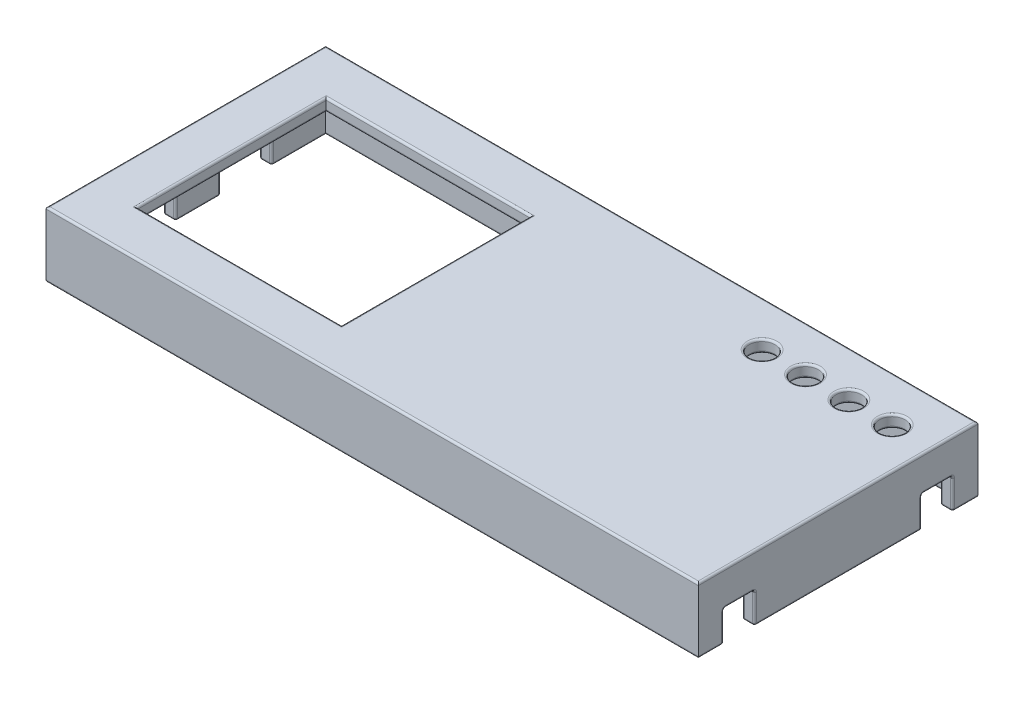
SolidWorks part; units mm, degrees
ref_plane "Front Plane" through (0, 0, 0) normal (0, 0, 1) x (1, 0, 0)
ref_plane "Top Plane" through (0, 0, 0) normal (0, 1, 0) x (1, 0, 0)
ref_plane "Right Plane" through (0, 0, 0) normal (1, 0, 0) x (0, 0, -1)
sketch "Sketch1" plane through (0, 0, 0) normal (0, 1, 0) x (1, 0, 0)
  line L0 (-2.4, 2.4) -> (-2.4, -52.4)
  line L1 (0, 0) -> (123, 0)
  line L2 (0, 0) -> (0, -50)
  line L3 (0, -50) -> (123, -50)
  line L4 (123, 0) -> (123, -50)
  line L5 (-2.4, -52.4) -> (125.4, -52.4)
  line L6 (125.4, 2.4) -> (125.4, -52.4)
  line L7 (-2.4, 2.4) -> (125.4, 2.4)
  dimension "D1" = 50
  dimension "D2" = 123
  dimension "D3" = 2.4
extrude "Boss-Extrude1" add sketch "Sketch1" along normal blind 10.4
sketch "Sketch2" plane through (0, 10.4, 0) normal (0, 1, 0) x (1, 0, 0)
  line L1 (-2.4, 2.4) -> (125.4, 2.4)
  line L2 (-2.4, 2.4) -> (-2.4, -52.4)
  line L3 (-2.4, -52.4) -> (125.4, -52.4)
  line L4 (125.4, 2.4) -> (125.4, -52.4)
extrude "Boss-Extrude2" add sketch "Sketch2" along normal blind 2.4
sketch "Sketch3" plane through (-2.4, 0, 0) normal (-1, 0, 0) x (0, 0, 1)
  line L0 (-2.4, 0) -> (52.4, 0) construction
  line L1 (10.6, 0) -> (20.6, 0)
  line L2 (10.6, 0) -> (10.6, 5)
  line L3 (10.6, 5) -> (20.6, 5)
  line L4 (20.6, 0) -> (20.6, 5)
  line L5 (-2.4, 12.8) -> (-2.4, 0) construction
  line L6 (29.4, 0) -> (39.4, 0)
  line L7 (29.4, 0) -> (29.4, 5)
  line L8 (29.4, 5) -> (39.4, 5)
  line L9 (39.4, 0) -> (39.4, 5)
  line L10 (52.4, 12.8) -> (52.4, 0) construction
  dimension "D1" = 10
  dimension "D2" = 10
  dimension "D3" = 5
  dimension "D4" = 5
  dimension "D5" = 13
  dimension "D6" = 13
extrude "Cut-Extrude1" cut sketch "Sketch3" against normal blind 10
sketch "Sketch4" plane through (0, 12.8, 0) normal (0, 1, 0) x (1, 0, 0)
  line L0 (-2.4, 2.4) -> (-2.4, -52.4) construction
  line L1 (6.6, -6.5) -> (46.6, -6.5)
  line L2 (6.6, -6.5) -> (6.6, -43.5)
  line L3 (6.6, -43.5) -> (46.6, -43.5)
  line L4 (46.6, -6.5) -> (46.6, -43.5)
  line L5 (125.4, 2.4) -> (-2.4, 2.4) construction
  dimension "D1" = 37
  dimension "D2" = 40
  dimension "D3" = 9
  dimension "D4" = 8.9
extrude "Cut-Extrude2" cut sketch "Sketch4" against normal blind 10
sketch "Sketch5" plane through (125.4, 0, 0) normal (1, 0, 0) x (0, 0, -1)
  line L0 (-52.4, 0) -> (2.4, 0) construction
  line L1 (-8.6, 0) -> (-2.6, 0)
  line L2 (-8.6, 0) -> (-8.6, 6)
  line L3 (-8.6, 6) -> (-2.6, 6)
  line L4 (-2.6, 0) -> (-2.6, 6)
  line L5 (2.4, 12.8) -> (2.4, 0) construction
  line L6 (-41.4, 0) -> (-47.4, 0)
  line L7 (-41.4, 0) -> (-41.4, 6)
  line L8 (-41.4, 6) -> (-47.4, 6)
  line L9 (-47.4, 0) -> (-47.4, 6)
  line L10 (-52.4, 12.8) -> (-52.4, 0) construction
  dimension "D1" = 6
  dimension "D2" = 6
  dimension "D3" = 6
  dimension "D4" = 6
  dimension "D5" = 5
  dimension "D6" = 5
extrude "Cut-Extrude3" cut sketch "Sketch5" against normal blind 10
sketch "Sketch6" plane through (0, 0, -2.4) normal (0, 0, -1) x (-1, 0, 0)
  line L0 (-125.4, 0) -> (2.4, 0) construction
  line L1 (-79.4, 0) -> (-64.4, 0)
  line L2 (-79.4, 0) -> (-79.4, 10)
  line L3 (-79.4, 10) -> (-64.4, 10)
  line L4 (-64.4, 0) -> (-64.4, 10)
  line L5 (-125.4, 12.8) -> (-125.4, 0) construction
  dimension "D1" = 15
  dimension "D2" = 10
  dimension "D3" = 46
extrude "Cut-Extrude4" cut sketch "Sketch6" against normal blind 10
sketch "Sketch7" plane through (0, 10.4, 0) normal (0, -1, 0) x (-1, 0, 0)
  circle A0 centre (-117.5, -6.5) radius 2.5
  circle A1 centre (-109, -6.5) radius 2.5
  circle A2 centre (-100.5, -6.5) radius 2.5
  circle A3 centre (-92, -6.5) radius 2.5
  dimension "D1" = 5
  dimension "D2" = 5
  dimension "D3" = 5
  dimension "D4" = 5
extrude "Cut-Extrude5" cut sketch "Sketch7" against normal blind 10
fillet "Fillet1" radius 0.4 12 edges at (61.5, 12.8, -2.4) (125.4, 12.8, 25) (61.5, 12.8, 52.4) (-2.4, 12.8, 25) (26.6, 12.8, 43.5) (46.6, 12.8, 25) (26.6, 12.8, 6.5) (6.6, 12.8, 25) (92, 12.8, 9) (100.5, 12.8, 9) (109, 12.8, 9) (117.5, 12.8, 9)
fillet "Fillet2" radius 0.4 68 edges at (123, 3, 8.6) (125.4, 3, 8.6) (125.4, 3, 2.6) (123, 3, 2.6) (123, 3, 47.4) (125.4, 3, 47.4) (125.4, 3, 41.4) (123, 3, 41.4) (79.4, 5, 0) (79.4, 5, -2.4) (64.4, 5, -2.4) (64.4, 5, 0) (0, 2.5, 10.6) (-2.4, 2.5, 10.6) (-2.4, 2.5, 20.6) (0, 2.5, 20.6) (0, 2.5, 29.4) (-2.4, 2.5, 29.4) (-2.4, 2.5, 39.4) (0, 2.5, 39.4) (124.2, 6, 8.6) (125.4, 6, 5.6) (124.2, 6, 2.6) (123, 6, 5.6) (124.2, 6, 47.4) (125.4, 6, 44.4) (124.2, 6, 41.4) (123, 6, 44.4) (123, 0, 25) (124.2, 0, 41.4) (125.4, 0, 25) (124.2, 0, 8.6) (101.2, 0, 0) (123, 0, 1.3) (124.2, 0, 2.6) (125.4, 0, 0.1) (102.4, 0, -2.4) (79.4, 0, -1.2) (79.4, 10, -1.2) (71.9, 10, -2.4) (64.4, 10, -1.2) (71.9, 10, 0) (-2.4, 0, 25) (-1.2, 0, 29.4) (0, 0, 25) (-1.2, 0, 20.6) (-1.2, 5, 10.6) (-2.4, 5, 15.6) (-1.2, 5, 20.6) (0, 5, 15.6) (-1.2, 5, 29.4) (-2.4, 5, 34.4) (-1.2, 5, 39.4) (0, 5, 34.4) (31, 0, -2.4) (-2.4, 0, 4.1) (-1.2, 0, 10.6) (0, 0, 5.3) (32.2, 0, 0) (64.4, 0, -1.2) (123, 0, 48.7) (61.5, 0, 50) (0, 0, 44.7) (-1.2, 0, 39.4) (-2.4, 0, 45.9) (61.5, 0, 52.4) (125.4, 0, 49.9) (124.2, 0, 47.4)
fillet "Fillet3" radius 0.4 4 edges at (117.5, 10.4, 4) (109, 10.4, 4) (100.5, 10.4, 4) (92, 10.4, 4)
fillet "Fillet4" radius 0.4 4 edges at (26.6, 10.4, 43.5) (6.6, 10.4, 25) (26.6, 10.4, 6.5) (46.6, 10.4, 25)
equation "\"D4@Sketch4\"=50/2+2.4-18.5"
